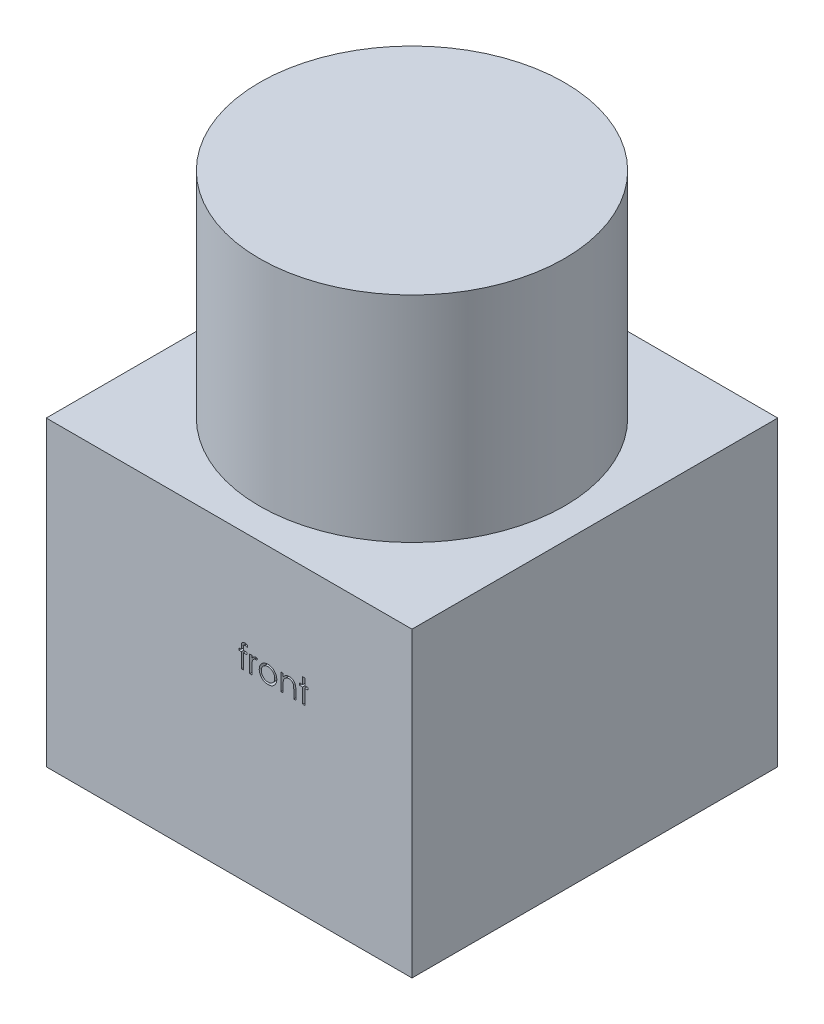
SolidWorks part; units mm, degrees
ref_plane "Front Plane" through (0, 0, 0) normal (0, 0, 1) x (1, 0, 0)
ref_plane "Top Plane" through (0, 0, 0) normal (0, 1, 0) x (1, 0, 0)
ref_plane "Right Plane" through (0, 0, 0) normal (1, 0, 0) x (0, 0, -1)
sketch "Sketch1" plane through (0, 0, 0) normal (0, 0, 1) x (1, 0, 0)
  line L1 (0, 0) -> (50, 0)
  line L2 (0, 0) -> (0, 41.3)
  line L3 (0, 41.3) -> (50, 41.3)
  line L4 (50, 0) -> (50, 41.3)
  dimension "D1" = 50
  dimension "D2" = 41.3
extrude "Boss-Extrude1" add sketch "Sketch1" along normal blind 50
sketch "Sketch2" plane through (0, 41.3, 0) normal (0, 1, 0) x (1, 0, 0)
  circle A0 centre (25, -25) radius 20.85
  dimension "D1" = 41.7
extrude "Boss-Extrude2" add sketch "Sketch2" along normal blind 29.3
sketch "Sketch3" plane through (0, 0, 0) normal (0, -1, 0) x (1, 0, 0)
  line L0 (45.864, 45.864) -> (47.564, 45.864)
  line L1 (50, 50) -> (0, 0) construction
  line L2 (4.136, 4.136) -> (2.436, 4.136) construction
  circle A0 centre (45.864, 45.864) radius 1.7
  circle A1 centre (4.136, 4.136) radius 1.7
  point P9 (0, 0)
  dimension "D1" = 1.7
  dimension "D2" = 4.8
  dimension "D3" = 1.7
  dimension "D4" = 4.8
extrude "Cut-Extrude1" cut sketch "Sketch3" against normal blind 12.7 contours A0 | A1
sketch "Sketch4" plane through (0, 0, 50) normal (0, 0, 1) x (1, 0, 0)
  text T0 "front"
extrude "Cut-Extrude2" cut sketch "Sketch4" against normal blind 2.54
